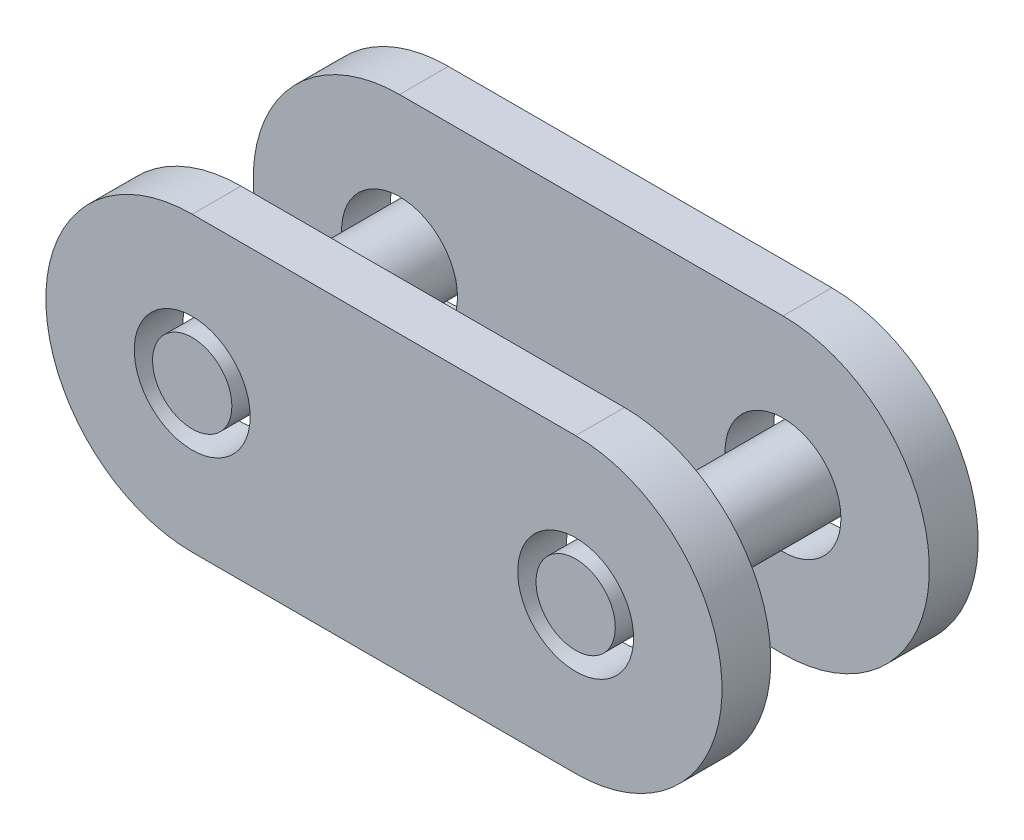
SolidWorks part; units mm, degrees
note: '?' marks a value the reader was unsure of.
material "Plain Carbon Steel"
ref_plane "Front Plane" through (0, 0, 0) normal (0, 0, 1) x (1, 0, 0)
ref_plane "Top Plane" through (0, 0, 0) normal (0, 1, 0) x (1, 0, 0)
ref_plane "Right Plane" through (0, 0, 0) normal (1, 0, 0) x (0, 0, -1)
ref_plane "Plane1" through (6.2876, 0, 0) normal (1, 0, 0) x (0, 0, -1)
sketch "Sketch1" plane through (0, 0, 0) normal (0, 0, 1) x (1, 0, 0)
  line L0 (0, -2.4) -> (6.2876, -2.4)
  line L1 (6.2876, 2.4) -> (0, 2.4)
  arc A0 (6.2876, -2.4) -> (6.2876, 2.4) centre (6.2876, 0) ccw
  arc A1 (0, 2.4) -> (0, -2.4) centre (0, 0) ccw
  circle A2 centre (0, 0) radius 0.95
  circle A3 centre (6.2876, 0) radius 0.95
  dimension "D2" = 2.4
  dimension "D3" = 2.4
  dimension "D4" = 1.9
  dimension "D6" = 1.9
  dimension "D1" = 6.2876
  dimension "D5" = 6.2876
extrude "Boss-Extrude1" add sketch "Sketch1" along normal blind 0.8 from offset 1.3
sketch "Sketch2" plane through (0, 0, 0) normal (0, 0, 1) x (1, 0, 0)
  line L0 (0, -2.4) -> (6.2876, -2.4)
  line L1 (6.2876, 2.4) -> (0, 2.4)
  arc A0 (6.2876, -2.4) -> (6.2876, 2.4) centre (6.2876, 0) ccw
  arc A1 (0, 2.4) -> (0, -2.4) centre (0, 0) ccw
  circle A2 centre (0, 0) radius 0.95
  circle A3 centre (6.2876, 0) radius 0.95
  dimension "D2" = 2.4
  dimension "D3" = 2.4
  dimension "D4" = 1.9
  dimension "D6" = 1.9
  dimension "D1" = 6.2876
  dimension "D5" = 6.2876
extrude "Boss-Extrude2" add sketch "Sketch2" along normal blind 0.8 from offset 2.1
sketch "Sketch3" plane through (0, 0, 0) normal (0, 0, 1) x (1, 0, 0)
  circle A0 centre (0, 0) radius 0.65
  circle A1 centre (6.2876, 0) radius 0.65
  dimension "D1" = 1.3
  dimension "D3" = 1.3
  dimension "D2" = 6.2876
extrude "Boss-Extrude3" add sketch "Sketch3" along normal blind 4.2 from offset 2.1
ref_axis "Axis1" through (0, 0, -2.31) along (0, 0, 1)?
ref_axis "Axis2" through (6.2876, 0, -2.31) along (0, 0, 1)?
